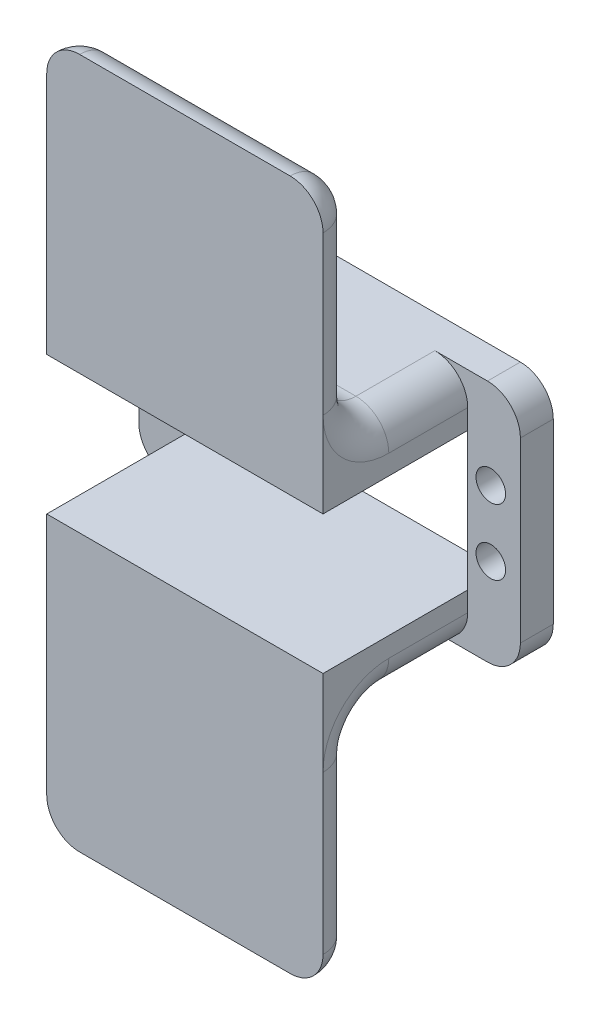
SolidWorks part; units mm, degrees
ref_plane "Front Plane" through (0, 0, 0) normal (0, 0, 1) x (1, 0, 0)
ref_plane "Top Plane" through (0, 0, 0) normal (0, 1, 0) x (1, 0, 0)
ref_plane "Right Plane" through (0, 0, 0) normal (1, 0, 0) x (0, 0, -1)
sketch "Sketch1" plane through (0, 0, 0) normal (0, 0, 1) x (1, 0, 0)
  line L0 (0, 10.5) -> (0, -10.5) construction
  line L1 (21, -10.5) -> (-21, -10.5)
  line L2 (21, -10.5) -> (21, 10.5)
  line L3 (21, 10.5) -> (-21, 10.5)
  line L4 (-21, -10.5) -> (-21, 10.5)
  line L5 (21, -10.5) -> (-21, 10.5) construction
  line L6 (21, 10.5) -> (-21, -10.5) construction
  line L7 (29, -18.5) -> (-29, -18.5)
  line L8 (29, -18.5) -> (29, 18.5)
  line L9 (29, 18.5) -> (-29, 18.5)
  line L10 (-29, -18.5) -> (-29, 18.5)
  line L11 (29, -18.5) -> (-29, 18.5) construction
  line L12 (29, 18.5) -> (-29, -18.5) construction
  line L13 (-21, 0) -> (21, 0) construction
  circle A0 centre (-24.5, 5) radius 2.25
  circle A1 centre (-24.5, -5) radius 2.25
  circle A2 centre (24.5, 5) radius 2.25
  circle A3 centre (24.5, -5) radius 2.25
  point P0 (0, 0)
  point P6 (0, 0)
  dimension "D6" = 4.5
  dimension "D1" = 42
  dimension "D2" = 21
  dimension "D3" = 8
  dimension "D5" = 10
  dimension "D8" = 8
  dimension "D4" = 24.5
  dimension "D7" = 5
extrude "Boss-Extrude1" add sketch "Sketch1" along normal blind 5
ref_plane "Plane1" through (0, 0, 5) normal (0, 0, 1) x (1, 0, 0)
sketch "Sketch2" plane through (0, 0, 5) normal (0, 0, 1) x (1, 0, 0)
  line L0 (-21, 18.5) -> (-21, 10.5)
  line L1 (29, 18.5) -> (-29, 18.5) construction
  line L2 (-21, 10.5) -> (21, 10.5)
  line L3 (21, 10.5) -> (21, 18.5)
  line L4 (21, 18.5) -> (-21, 18.5)
  line L5 (-21, -10.5) -> (-21, -18.5)
  line L6 (-29, -18.5) -> (29, -18.5) construction
  line L7 (-21, -18.5) -> (21, -18.5)
  line L8 (21, -18.5) -> (21, -10.5)
  line L9 (-21, -10.5) -> (21, -10.5) construction
  line L10 (21, -10.5) -> (-21, -10.5)
extrude "Boss-Extrude2" add sketch "Sketch2" along normal blind 17
ref_plane "Plane2" through (0, 0, 22) normal (0, 0, 1) x (1, 0, 0)
sketch "Sketch3" plane through (0, 0, 22) normal (0, 0, 1) x (1, 0, 0)
  line L0 (21, -18.5) -> (21, -10.5) construction
  line L1 (-21, -10.5) -> (21, -10.5)
  line L2 (-21, -10.5) -> (-21, -52.5)
  line L3 (-21, -52.5) -> (21, -52.5)
  line L4 (21, -10.5) -> (21, -52.5)
  line L5 (21, 10.5) -> (21, 18.5) construction
  line L6 (-21, 10.5) -> (21, 10.5)
  line L7 (-21, 10.5) -> (-21, 52.5)
  line L8 (-21, 52.5) -> (21, 52.5)
  line L9 (21, 10.5) -> (21, 52.5)
  dimension "D1" = 42
extrude "Boss-Extrude3" add sketch "Sketch3" along normal blind 5
fillet "Fillet1" radius 5 1 edges
fillet "Fillet2" radius 5 1 edges
fillet "Fillet3" radius 5 1 edges at (0, 52.5, 22)
fillet "Fillet4" radius 5 1 edges at (0, -52.5, 22)
fillet "Fillet5" radius 5 8 edges at (-21, 51.0355, 23.4645) (-21, 19.9645, 20.5355) (21, 19.9645, 20.5355) (21, 51.0355, 23.4645)
fillet "Fillet6" radius 5 8 edges at (-21, -19.9645, 20.5355) (-21, -51.0355, 23.4645) (21, -51.0355, 23.4645) (21, -19.9645, 20.5355)
fillet "Fillet7" radius 5 4 edges at (-29, 18.5, 2.5) (-29, -18.5, 2.5) (29, -18.5, 2.5) (29, 18.5, 2.5)
equation "\"D8@Sketch1\"=\"D3@Sketch1\""
equation "\"D1@Sketch3\"=2*\"D2@Sketch1\""
